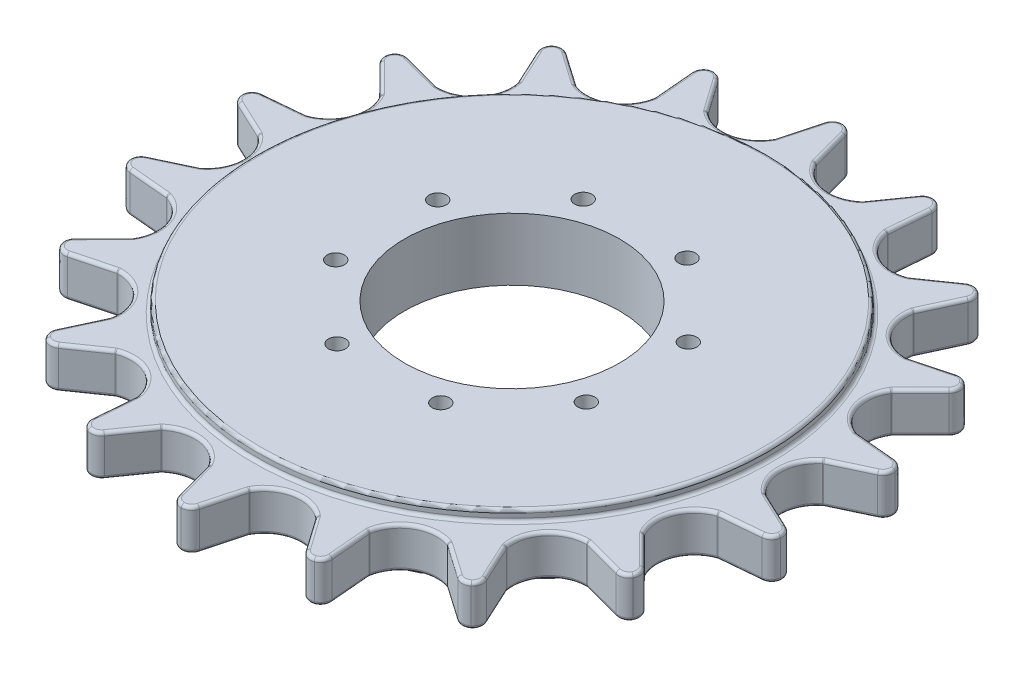
SolidWorks part; units mm, degrees
ref_plane "Ön Düzlem" through (0, 0, 0) normal (0, 0, 1) x (1, 0, 0)
ref_plane "Üst Düzlem" through (0, 0, 0) normal (0, 1, 0) x (1, 0, 0)
ref_plane "Sağ Düzlem" through (0, 0, 0) normal (1, 0, 0) x (0, 0, -1)
sketch "Çizim1" plane through (0, 0, 0) normal (0, 1, 0) x (1, 0, 0)
  line L0 (-19.4548, 263.3797) -> (-7.5, 307.4085)
  line L1 (19.4548, 263.3797) -> (7.5, 307.4085)
  line L2 (108.3627, 240.8421) -> (112.1876, 286.3044)
  line L3 (71.7997, 254.1499) -> (98.0922, 291.4347)
  line L4 (184.2004, 189.2553) -> (203.3437, 230.6677)
  line L5 (154.394, 214.2659) -> (191.8531, 240.3095)
  line L6 (237.8209, 114.8416) -> (269.9736, 147.2091)
  line L7 (218.3662, 148.5382) -> (262.4736, 160.1995)
  line L8 (262.7567, 26.5762) -> (304.0407, 45.9949)
  line L9 (256.0001, 64.8946) -> (301.4359, 60.767)
  line L10 (256.0001, -64.8946) -> (301.4359, -60.767)
  line L11 (262.7567, -26.5762) -> (304.0407, -45.9949)
  line L12 (218.3662, -148.5382) -> (262.4736, -160.1995)
  line L13 (237.8209, -114.8416) -> (269.9736, -147.2091)
  line L14 (154.394, -214.2659) -> (191.8531, -240.3095)
  line L15 (184.2004, -189.2553) -> (203.3437, -230.6677)
  line L16 (71.7997, -254.1499) -> (98.0922, -291.4347)
  line L17 (108.3627, -240.8421) -> (112.1876, -286.3044)
  line L18 (-19.4548, -263.3797) -> (-7.5, -307.4085)
  line L19 (19.4548, -263.3797) -> (7.5, -307.4085)
  line L20 (-108.3627, -240.8421) -> (-112.1876, -286.3044)
  line L21 (-71.7997, -254.1499) -> (-98.0922, -291.4347)
  line L22 (-184.2004, -189.2553) -> (-203.3437, -230.6677)
  line L23 (-154.394, -214.2659) -> (-191.8531, -240.3095)
  line L24 (-237.8209, -114.8416) -> (-269.9736, -147.2091)
  line L25 (-218.3662, -148.5382) -> (-262.4736, -160.1995)
  line L26 (-262.7567, -26.5762) -> (-304.0407, -45.9949)
  line L27 (-256.0001, -64.8946) -> (-301.4359, -60.767)
  line L28 (-256.0001, 64.8946) -> (-301.4359, 60.767)
  line L29 (-262.7567, 26.5762) -> (-304.0407, 45.9949)
  line L30 (-218.3662, 148.5382) -> (-262.4736, 160.1995)
  line L31 (-237.8209, 114.8416) -> (-269.9736, 147.2091)
  line L32 (-154.394, 214.2659) -> (-191.8531, 240.3095)
  line L33 (-184.2004, 189.2553) -> (-203.3437, 230.6677)
  line L34 (-71.7997, 254.1499) -> (-98.0922, 291.4347)
  line L35 (-108.3627, 240.8421) -> (-112.1876, 286.3044)
  arc A0 (-191.8531, 240.3095) -> (-203.3437, 230.6677) centre (0, 0) ccw
  arc A1 (108.3627, 240.8421) -> (154.394, 214.2659) centre (142.0308, 246.0046) ccw
  arc A2 (-98.0922, 291.4347) -> (-112.1876, 286.3044) centre (0, 0) ccw
  arc A3 (7.5, 307.4085) -> (-7.5, 307.4085) centre (0, 0) ccw
  arc A4 (112.1876, 286.3044) -> (98.0922, 291.4347) centre (0, 0) ccw
  arc A5 (203.3437, 230.6677) -> (191.8531, 240.3095) centre (0, 0) ccw
  arc A6 (269.9736, 147.2091) -> (262.4736, 160.1995) centre (0, 0) ccw
  arc A7 (304.0407, 45.9949) -> (301.4359, 60.767) centre (0, 0) ccw
  arc A8 (301.4359, -60.767) -> (304.0407, -45.9949) centre (0, 0) ccw
  arc A9 (262.4736, -160.1995) -> (269.9736, -147.2091) centre (0, 0) ccw
  arc A10 (191.8531, -240.3095) -> (203.3437, -230.6677) centre (0, 0) ccw
  arc A11 (98.0922, -291.4347) -> (112.1876, -286.3044) centre (0, 0) ccw
  arc A12 (-7.5, -307.4085) -> (7.5, -307.4085) centre (0, 0) ccw
  arc A13 (-112.1876, -286.3044) -> (-98.0922, -291.4347) centre (0, 0) ccw
  arc A14 (-203.3437, -230.6677) -> (-191.8531, -240.3095) centre (0, 0) ccw
  arc A15 (-269.9736, -147.2091) -> (-262.4736, -160.1995) centre (0, 0) ccw
  arc A16 (-304.0407, -45.9949) -> (-301.4359, -60.767) centre (0, 0) ccw
  arc A17 (-301.4359, 60.767) -> (-304.0407, 45.9949) centre (0, 0) ccw
  arc A18 (-262.4736, 160.1995) -> (-269.9736, 147.2091) centre (0, 0) ccw
  arc A19 (19.4548, 263.3797) -> (71.7997, 254.1499) centre (49.3268, 279.7461) ccw
  arc A20 (184.2004, 189.2553) -> (218.3662, 148.5382) centre (217.6039, 182.5913) ccw
  arc A21 (237.8209, 114.8416) -> (256.0001, 64.8946) centre (266.9307, 97.1548) ccw
  arc A22 (262.7567, 26.5762) -> (262.7567, -26.5762) centre (284.0617, 0) ccw
  arc A23 (256.0001, -64.8946) -> (237.8209, -114.8416) centre (266.9307, -97.1548) ccw
  arc A24 (218.3662, -148.5382) -> (184.2004, -189.2553) centre (217.6039, -182.5913) ccw
  arc A25 (154.394, -214.2659) -> (108.3627, -240.8421) centre (142.0308, -246.0046) ccw
  arc A26 (71.7997, -254.1499) -> (19.4548, -263.3797) centre (49.3268, -279.7461) ccw
  arc A27 (-19.4548, -263.3797) -> (-71.7997, -254.1499) centre (-49.3268, -279.7461) ccw
  arc A28 (-108.3627, -240.8421) -> (-154.394, -214.2659) centre (-142.0308, -246.0046) ccw
  arc A29 (-184.2004, -189.2553) -> (-218.3662, -148.5382) centre (-217.6039, -182.5913) ccw
  arc A30 (-237.8209, -114.8416) -> (-256.0001, -64.8946) centre (-266.9307, -97.1548) ccw
  arc A31 (-262.7567, -26.5762) -> (-262.7567, 26.5762) centre (-284.0617, 0) ccw
  arc A32 (-256.0001, 64.8946) -> (-237.8209, 114.8416) centre (-266.9307, 97.1548) ccw
  arc A33 (-218.3662, 148.5382) -> (-184.2004, 189.2553) centre (-217.6039, 182.5913) ccw
  arc A34 (-154.394, 214.2659) -> (-108.3627, 240.8421) centre (-142.0308, 246.0046) ccw
  arc A35 (-71.7997, 254.1499) -> (-19.4548, 263.3797) centre (-49.3268, 279.7461) ccw
  circle A36 centre (0, 0) radius 100
  dimension "D1" = 200
extrude "Yükseklik-Ekstrüzyon1" add sketch "Çizim1" along normal mid plane 58
fillet "Radyus1" radius 10 36 edges at (7.5, 0, -307.4085) (-7.5, 0, -307.4085) (191.8531, 0, 240.3095) (203.3437, 0, 230.6677) (262.4736, 0, 160.1995) (269.9736, 0, 147.2091) (301.4359, 0, 60.767) (304.0407, 0, 45.9949) (304.0407, 0, -45.9949) (301.4359, 0, -60.767) (269.9736, 0, -147.2091) (262.4736, 0, -160.1995) (203.3437, 0, -230.6677) (191.8531, 0, -240.3095) (98.0922, 0, -291.4347) (112.1876, 0, -286.3044) (112.1876, 0, 286.3044) (98.0922, 0, 291.4347) (7.5, 0, 307.4085) (-7.5, 0, 307.4085) (-98.0922, 0, 291.4347) (-112.1876, 0, 286.3044) (-203.3437, 0, 230.6677) (-191.8531, 0, 240.3095) (-269.9736, 0, 147.2091) (-262.4736, 0, 160.1995) (-301.4359, 0, 60.767) (-304.0407, 0, 45.9949) (-304.0407, 0, -45.9949) (-301.4359, 0, -60.767) (-269.9736, 0, -147.2091) (-262.4736, 0, -160.1995) (-203.3437, 0, -230.6677) (-191.8531, 0, -240.3095) (-112.1876, 0, -286.3044) (-98.0922, 0, -291.4347)
sketch "Çizim2" plane through (0, 29, 0) normal (0, 1, 0) x (1, 0, 0)
  line L0 (0, 0) -> (0, 151.96)
  line L1 (0, 0) -> (58.1339, 143.8865)
  circle A1 centre (0, 0) radius 125
  circle A2 centre (46.8258, 115.898) radius 8
  dimension "D1" = 250
  dimension "D4" = 16
  dimension "D2" = 22
extrude "Kes-Ekstrüzyon1" cut sketch "Çizim2" against normal up to next contours A1 A2 L1 | L1 A2 A1 | A1 A2 L1 | L1 A2 A1 region at (42.422, 29, -113.966) region at (48.6516, 29, -111.4491) region at (44.8999, 29, -120.2879) region at (51.2607, 29, -117.7179)
pattern_circular "Dairesel Çoğaltma1" count 8 over 360 about axis through (0, 29, 0) along (0, -1, 0) of "Kes-Ekstrüzyon1"
sketch "Çizim3" plane through (0, 0, 0) normal (1, 0, 0) x (0, 0, -1)
  line L0 (307.4985, 29) -> (300.1203, 29) construction
  line L1 (309.8731, 30.5535) -> (237.4985, 30.5535)
  line L2 (309.8731, 30.5535) -> (309.8731, 19)
  line L3 (309.8731, 19) -> (237.4985, 19)
  line L4 (237.4985, 30.5535) -> (237.4985, 19)
  line L5 (307.4985, 29) -> (307.4985, -29) construction
  line L6 (307.4985, 0) -> (284.5997, 0) construction
  line L7 (237.4985, -30.5535) -> (237.4985, -19)
  line L8 (309.8731, -19) -> (237.4985, -19)
  line L9 (309.8731, -30.5535) -> (309.8731, -19)
  line L10 (309.8731, -30.5535) -> (237.4985, -30.5535)
  dimension "D1" = 10
  dimension "D2" = 70
sketch "Çizim5" plane through (0, 0, 0) normal (0, 1, 0) x (1, 0, 0)
  circle A0 centre (0, 0) radius 307.4985
sweep "Kes-Süpür1" cut profiles "Çizim3" path "Çizim5"
fillet "Radyus2" radius 3 2 edges at (0, 19, -237.4985) (0, -19, -237.4985)
fillet "Radyus3" radius 3 216 edges at (-299.7148, -19, -58.9106) (-274.9575, -19, -63.1724) (-301.7884, -19, -47.1506) (-299.7148, 19, -58.9106) (-234.9232, -19, -85.505) (-256.0001, 0, -64.8946) (-274.9575, 19, -63.1724) (-279.9817, -19, -34.6783) (-301.7884, 19, -47.1506) (-251.2361, -19, -128.3464) (-237.8209, 0, -114.8416) (-234.9232, 19, -85.505) (-250, -19, 0) (-262.7567, 0, -26.5762) (-279.9817, 19, -34.6783) (-267.4619, -19, -147.5248) (-251.2361, 19, -128.3464) (-279.9817, -19, 34.6783) (-262.7567, 0, 26.5762) (-250, 19, 0) (-261.4912, -19, -157.8664) (-267.4619, 19, -147.5248) (-301.7884, -19, 47.1506) (-279.9817, 19, 34.6783) (-236.7693, -19, -153.4037) (-261.4912, 19, -157.8664) (-299.7148, -19, 58.9106) (-301.7884, 19, 47.1506) (-191.5111, -19, -160.6969) (-218.3662, 0, -148.5382) (-236.7693, 19, -153.4037) (-274.9575, -19, 63.1724) (-299.7148, 19, 58.9106) (-192.1877, -19, -206.5339) (-184.2004, 0, -189.2553) (-191.5111, 19, -160.6969) (-234.9232, -19, 85.505) (-256.0001, 0, 64.8946) (-274.9575, 19, 63.1724) (-200.8755, -19, -230.1053) (-192.1877, 19, -206.5339) (-251.2361, -19, 128.3464) (-237.8209, 0, 114.8416) (-234.9232, 19, 85.505) (-191.7279, -19, -237.7811) (-200.8755, 19, -230.1053) (-267.4619, -19, 147.5248) (-251.2361, 19, 128.3464) (-170.0232, -19, -225.1321) (-191.7279, 19, -237.7811) (-261.4912, -19, 157.8664) (-267.4619, 19, 147.5248) (-125, -19, -216.5064) (-154.394, 0, -214.2659) (-170.0232, 19, -225.1321) (-236.7693, -19, 153.4037) (-261.4912, 19, 157.8664) (-109.9586, -19, -259.8105) (-108.3627, 0, -240.8421) (-125, 19, -216.5064) (-191.5111, -19, 160.6969) (-218.3662, 0, 148.5382) (-236.7693, 19, 153.4037) (-110.0605, -19, -284.9317) (-109.9586, 19, -259.8105) (-192.1877, -19, 206.5339) (-184.2004, 0, 189.2553) (-191.5111, 19, 160.6969) (-98.8393, -19, -289.0159) (-110.0605, 19, -284.9317) (-200.8755, -19, 230.1053) (-192.1877, 19, 206.5339) (-82.7698, -19, -269.7064) (-98.8393, 19, -289.0159) (-191.7279, -19, 237.7811) (-200.8755, 19, 230.1053) (-43.412, -19, -246.2019) (-71.7997, 0, -254.1499) (-82.7698, 19, -269.7064) (-170.0232, -19, 225.1321) (-191.7279, 19, 237.7811) (-14.4668, -19, -281.75) (-19.4548, 0, -263.3797) (-43.412, 19, -246.2019) (-125, -19, 216.5064) (-154.394, 0, 214.2659) (-170.0232, 19, 225.1321) (-5.9707, -19, -305.3912) (-14.4668, 19, -281.75) (-109.9586, -19, 259.8105) (-108.3627, 0, 240.8421) (-125, 19, 216.5064) (5.9707, -19, -305.3912) (-5.9707, 19, -305.3912) (-110.0605, -19, 284.9317) (-109.9586, 19, 259.8105) (14.4668, -19, -281.75) (5.9707, 19, -305.3912) (-98.8393, -19, 289.0159) (-110.0605, 19, 284.9317) (43.412, -19, -246.2019) (19.4548, 0, -263.3797) (14.4668, 19, -281.75) (-82.7698, -19, 269.7064) (-98.8393, 19, 289.0159) (82.7698, -19, -269.7064) (71.7997, 0, -254.1499) (43.412, 19, -246.2019) (-43.412, -19, 246.2019) (-71.7997, 0, 254.1499) (-82.7698, 19, 269.7064) (98.8393, -19, -289.0159) (82.7698, 19, -269.7064) (-14.4668, -19, 281.75) (-19.4548, 0, 263.3797) (-43.412, 19, 246.2019) (110.0605, -19, -284.9317) (98.8393, 19, -289.0159) (-5.9707, -19, 305.3912) (-14.4668, 19, 281.75) (109.9586, -19, -259.8105) (110.0605, 19, -284.9317) (5.9707, -19, 305.3912) (-5.9707, 19, 305.3912) (125, -19, -216.5064) (108.3627, 0, -240.8421) (109.9586, 19, -259.8105) (14.4668, -19, 281.75) (5.9707, 19, 305.3912) (170.0232, -19, -225.1321) (154.394, 0, -214.2659) (125, 19, -216.5064) (43.412, -19, 246.2019) (19.4548, 0, 263.3797) (14.4668, 19, 281.75) (191.7279, -19, -237.7811) (170.0232, 19, -225.1321) (82.7698, -19, 269.7064) (71.7997, 0, 254.1499) (43.412, 19, 246.2019) (200.8755, -19, -230.1053) (191.7279, 19, -237.7811) (98.8393, -19, 289.0159) (82.7698, 19, 269.7064) (192.1877, -19, -206.5339) (200.8755, 19, -230.1053) (110.0605, -19, 284.9317) (98.8393, 19, 289.0159) (191.5111, -19, -160.6969) (184.2004, 0, -189.2553) (192.1877, 19, -206.5339) (109.9586, -19, 259.8105) (110.0605, 19, 284.9317) (236.7693, -19, -153.4037) (218.3662, 0, -148.5382) (191.5111, 19, -160.6969) (125, -19, 216.5064) (108.3627, 0, 240.8421) (109.9586, 19, 259.8105) (261.4912, -19, -157.8664) (236.7693, 19, -153.4037) (170.0232, -19, 225.1321) (154.394, 0, 214.2659) (125, 19, 216.5064) (267.4619, -19, -147.5248) (261.4912, 19, -157.8664) (191.7279, -19, 237.7811) (170.0232, 19, 225.1321) (251.2361, -19, -128.3464) (267.4619, 19, -147.5248) (200.8755, -19, 230.1053) (191.7279, 19, 237.7811) (234.9232, -19, -85.505) (237.8209, 0, -114.8416) (251.2361, 19, -128.3464) (192.1877, -19, 206.5339) (200.8755, 19, 230.1053) (274.9575, -19, -63.1724) (256.0001, 0, -64.8946) (234.9232, 19, -85.505) (191.5111, -19, 160.6969) (184.2004, 0, 189.2553) (192.1877, 19, 206.5339) (299.7148, -19, -58.9106) (274.9575, 19, -63.1724) (236.7693, -19, 153.4037) (218.3662, 0, 148.5382) (191.5111, 19, 160.6969) (301.7884, -19, -47.1506) (299.7148, 19, -58.9106) (261.4912, -19, 157.8664) (236.7693, 19, 153.4037) (279.9817, -19, -34.6783) (301.7884, 19, -47.1506) (301.7884, -19, 47.1506) (267.4619, -19, 147.5248) (261.4912, 19, 157.8664) (279.9817, -19, 34.6783) (250, -19, 0) (262.7567, 0, -26.5762) (279.9817, 19, -34.6783) (299.7148, -19, 58.9106) (251.2361, -19, 128.3464) (267.4619, 19, 147.5248) (262.7567, 0, 26.5762) (250, 19, 0) (234.9232, -19, 85.505) (274.9575, -19, 63.1724) (237.8209, 0, 114.8416) (251.2361, 19, 128.3464) (279.9817, 19, 34.6783) (256.0001, 0, 64.8946) (234.9232, 19, 85.505) (274.9575, 19, 63.1724) (299.7148, 19, 58.9106) (301.7884, 19, 47.1506)
fillet "Radyus4" radius 3 2 edges at (0, -29, 237.4985) (0, 29, 237.4985)
